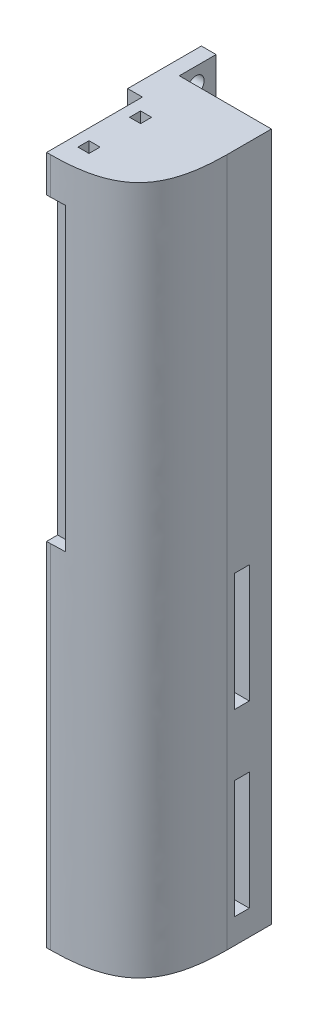
SolidWorks part; units mm, degrees
ref_plane "Front Plane" through (0, 0, 0) normal (0, 0, 1) x (1, 0, 0)
ref_plane "Top Plane" through (0, 0, 0) normal (0, 1, 0) x (1, 0, 0)
ref_plane "Right Plane" through (0, 0, 0) normal (1, 0, 0) x (0, 0, -1)
sketch "Sketch1" plane through (0, 0, 0) normal (0, 1, 0) x (1, 0, 0)
  line L1 (0, 0) -> (25, 0)
  line L2 (0, 0) -> (0, 36)
  line L3 (0, 36) -> (25, 36)
  line L4 (25, 0) -> (25, 36)
  dimension "D1" = 25
  dimension "D2" = 36
extrude "Boss-Extrude1" add sketch "Sketch1" along normal blind 186.9
fillet "Fillet1" radius 24 1 edges at (25, 93.45, 0) conic rho 0.55
ref_plane "Plane1" through (0, 0, 0) normal (0, 0, -1) x (-1, 0, 0)
sketch "Sketch2" plane through (0, 0, 0) normal (0, 0, -1) x (-1, 0, 0)
  line L1 (0, 176.9) -> (-5, 176.9)
  line L2 (0, 176.9) -> (0, 95.5)
  line L3 (0, 95.5) -> (-5, 95.5)
  line L4 (-5, 176.9) -> (-5, 95.5)
  line L5 (-1, 186.9) -> (-25, 186.9) construction
  dimension "D1" = 10
  dimension "D2" = 81.4
  dimension "D3" = 5
extrude "Cut-Extrude1" cut sketch "Sketch2" along normal blind 3
sketch "Sketch6" plane through (0, 0, -36) normal (0, 0, -1) x (-1, 0, 0)
  line L0 (0, 186.9) -> (0, 0) construction
  line L1 (0, 186.9) -> (4, 186.9)
  line L2 (0, 186.9) -> (0, 176.9)
  line L3 (0, 176.9) -> (4, 176.9)
  line L4 (4, 186.9) -> (4, 176.9)
  line L5 (0, 66.9) -> (4, 66.9)
  line L6 (0, 66.9) -> (0, 76.9)
  line L7 (0, 76.9) -> (4, 76.9)
  line L8 (4, 66.9) -> (4, 76.9)
  line L9 (-25, 186.9) -> (0, 186.9) construction
  dimension "D1" = 10
  dimension "D2" = 4
  dimension "D3" = 4
  dimension "D4" = 10
  dimension "D5" = 120
extrude "Boss-Extrude3" add sketch "Sketch6" against normal blind 10 and the other way blind 10
sketch "Sketch7" plane through (-4, 0, 0) normal (-1, 0, 0) x (0, 0, 1)
  line L0 (-36, 176.9) -> (-36, 76.9) construction
  line L1 (-46, 186.9) -> (-26, 186.9) construction
  line L2 (-46, 66.9) -> (-26, 66.9) construction
  line L3 (-36, 66.9) -> (-36, 0) construction
  circle A0 centre (-40.5, 182.4) radius 2.25
  circle A1 centre (-40.5, 71.4) radius 2.25
  dimension "D3" = 4.5
  dimension "D6" = 4.5
  dimension "D1" = 4.5
  dimension "D2" = 4.5
  dimension "D4" = 4.5
  dimension "D5" = 4.5
extrude "Cut-Extrude2" cut sketch "Sketch7" against normal up to next
chamfer "Chamfer1" distance 4 angle 45 1 edges at (0, 71.9, -26)
sketch "Sketch8" plane through (0, 0, 0) normal (-1, 0, 0) x (0, 0, 1)
  line L0 (-26, 186.9) -> (0, 186.9) construction
  line L1 (-10, 182.9) -> (-4, 182.9)
  line L2 (-10, 182.9) -> (-10, 178.9)
  line L3 (-10, 178.9) -> (-4, 178.9)
  line L4 (-4, 182.9) -> (-4, 178.9)
  line L5 (0, 13.75) -> (0, -13.75) construction
  line L7 (-24, 182.9) -> (-18, 182.9)
  line L8 (-24, 182.9) -> (-24, 178.9)
  line L9 (-24, 178.9) -> (-18, 178.9)
  line L10 (-18, 182.9) -> (-18, 178.9)
  dimension "D1" = 4
  dimension "D2" = 6
  dimension "D3" = 4
  dimension "D4" = 4
  dimension "D5" = 8
  dimension "D6" = 6
  dimension "D7" = 4
extrude "Cut-Extrude3" cut sketch "Sketch8" against normal blind 9
sketch "Sketch9" plane through (0, 186.9, 0) normal (0, 1, 0) x (1, 0, 0)
  line L0 (0, 0) -> (1, 0) construction
  line L1 (3, 5.5) -> (6, 5.5)
  line L2 (3, 5.5) -> (3, 8.5)
  line L3 (3, 8.5) -> (6, 8.5)
  line L4 (6, 5.5) -> (6, 8.5)
  line L5 (0, 26) -> (0, 0) construction
  line L7 (3, 19.5) -> (6, 19.5)
  line L8 (3, 19.5) -> (3, 22.5)
  line L9 (3, 22.5) -> (6, 22.5)
  line L10 (6, 19.5) -> (6, 22.5)
  dimension "D1" = 5.5
  dimension "D2" = 3
  dimension "D3" = 3
  dimension "D4" = 3
  dimension "D5" = 11
  dimension "D6" = 3
  dimension "D7" = 3
  dimension "D8" = 3
extrude "Cut-Extrude4" cut sketch "Sketch9" against normal blind 10
sketch "Sketch10" plane through (0, 0, 0) normal (0, -1, 0) x (1, 0, 0)
  line L0 (0, -36) -> (0, 0) construction
  line L1 (3, -5) -> (7, -5)
  line L2 (3, -5) -> (3, -33)
  line L3 (3, -33) -> (7, -33)
  line L4 (7, -5) -> (7, -29)
  line L5 (0, 0) -> (1, 0) construction
  line L6 (25, -36) -> (0, -36) construction
  line L7 (25, -24) -> (25, -36) construction
  line L8 (7, -33) -> (21, -33)
  line L10 (7, -29) -> (21, -29)
  line L11 (21, -33) -> (21, -29)
  dimension "D1" = 3
  dimension "D2" = 5
  dimension "D3" = 4
  dimension "D4" = 3
  dimension "D5" = 4
  dimension "D6" = 4
extrude "Boss-Extrude4" add sketch "Sketch10" along normal blind 4
sketch "Sketch11" plane through (0, 0, 0) normal (0, -1, 0) x (1, 0, 0)
  line L0 (21, -29) -> (7, -29) construction
  line L1 (7, -29) -> (7, -5) construction
  circle A0 centre (14, -22) radius 2
  dimension "D1" = 4
  dimension "D2" = 7
  dimension "D3" = 7
sketch "Sketch14" plane through (0, 0, 0) normal (0, 1, 0) x (-1, 0, 0)
  line L3 (0, -26) -> (0, 0) construction
  line L4 (-13.75, 0) -> (13.75, 0) construction
  circle A1 centre (-14, -11) radius 1.5
  dimension "D1" = 11
  dimension "D2" = 14
  dimension "D6" = 3
extrude "Cut-Extrude5" cut sketch "Sketch11" against normal blind 5
extrude "Cut-Extrude6" cut sketch "Sketch14" along normal blind 4
sketch "Sketch15" plane through (25, 0, 0) normal (1, 0, 0) x (0, 0, -1)
  line L0 (24, 186.9) -> (24, 0) construction
  line L1 (26, 87.5) -> (30, 87.5)
  line L2 (26, 87.5) -> (26, 55.5)
  line L3 (26, 55.5) -> (30, 55.5)
  line L4 (30, 87.5) -> (30, 55.5)
  line L6 (29, -4) -> (5, -4) construction
  line L7 (26, 38.8) -> (30, 38.8)
  line L8 (26, 38.8) -> (26, 6.8)
  line L9 (26, 6.8) -> (30, 6.8)
  line L10 (30, 38.8) -> (30, 6.8)
  dimension "D1" = 2
  dimension "D2" = 4
  dimension "D3" = 10.8
  dimension "D4" = 32
  dimension "D5" = 2
  dimension "D6" = 4
  dimension "D7" = 32
  dimension "D8" = 16.7
extrude "Cut-Extrude7" cut sketch "Sketch15" against normal blind 4
